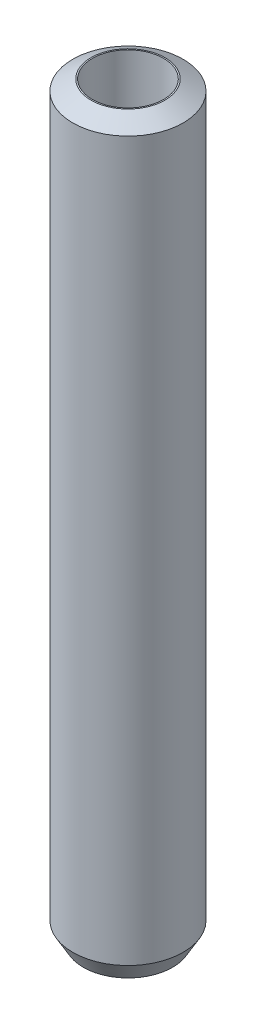
SolidWorks part; units mm, degrees
ref_plane "Front Plane" through (0, 0, 0) normal (0, 0, 1) x (1, 0, 0)
ref_plane "Top Plane" through (0, 0, 0) normal (0, 1, 0) x (1, 0, 0)
ref_plane "Right Plane" through (0, 0, 0) normal (1, 0, 0) x (0, 0, -1)
sketch "Sketch1" plane through (0, 0, 0) normal (0, 1, 0) x (1, 0, 0)
  circle A0 centre (0, 0) radius 22.5
  dimension "SHAFT_OD" = 45
extrude "Boss-Extrude1" add sketch "Sketch1" along normal blind 304.4932
sketch "Sketch2" plane through (0, 0, 0) normal (0, 1, 0) x (1, 0, 0)
  circle A0 centre (0, 0) radius 14.5182
  dimension "BORE_D" = 29.0364
extrude "Cut-Extrude1" cut sketch "Sketch2" along normal through all
chamfer "Chamfer1" distance 4.2943 angle 60 2 edges at (0, 304.4932, 22.5) (0, 0, 22.5) first distance on face at (0, 304.4932, 22.5) first distance on face at (0, 0, 14.5182)
